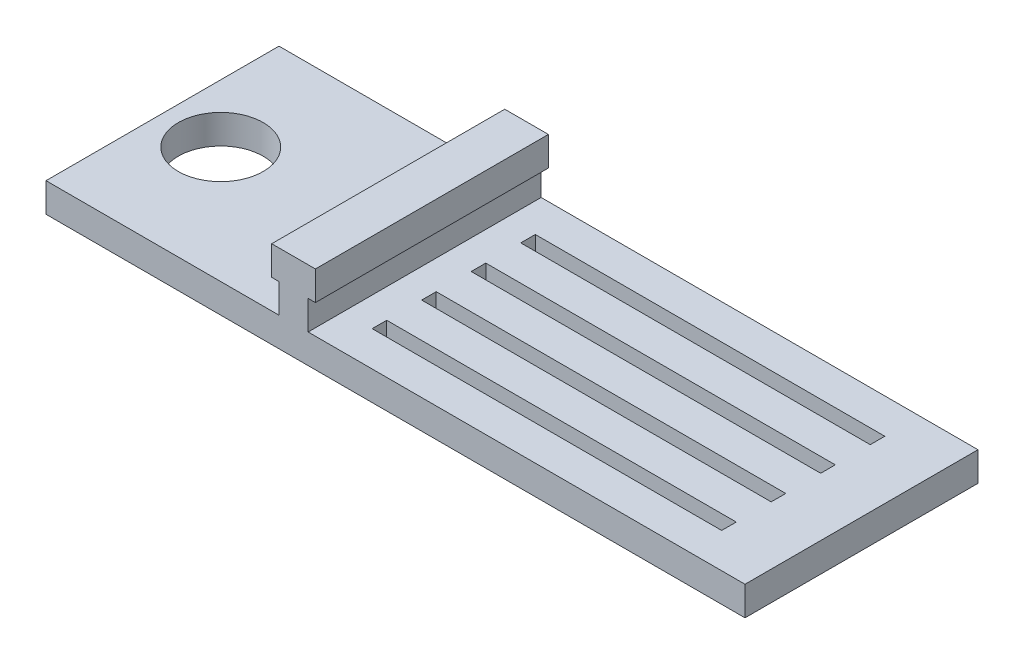
SolidWorks part; units mm, degrees
ref_plane "Front Plane" through (0, 0, 0) normal (0, 0, 1) x (1, 0, 0)
ref_plane "Top Plane" through (0, 0, 0) normal (0, 1, 0) x (1, 0, 0)
ref_plane "Right Plane" through (0, 0, 0) normal (1, 0, 0) x (0, 0, -1)
sketch "Sketch1" plane through (0, 0, 0) normal (0, 1, 0) x (1, 0, 0)
  line L1 (0, 0) -> (304.8, 0)
  line L2 (0, 0) -> (0, 101.6)
  line L3 (0, 101.6) -> (304.8, 101.6)
  line L4 (304.8, 0) -> (304.8, 101.6)
  dimension "D1" = 304.8
  dimension "4" = 101.6
extrude "Boss-Extrude1" add sketch "Sketch1" along normal blind 12.7
sketch "Sketch2" plane through (0, 12.7, 0) normal (0, 1, 0) x (1, 0, 0)
  line L1 (127, 21.5701) -> (279.4, 21.5701)
  line L2 (127, 21.5701) -> (127, 15.2201)
  line L3 (127, 15.2201) -> (279.4, 15.2201)
  line L4 (279.4, 21.5701) -> (279.4, 15.2201)
  line L5 (304.8, 0) -> (304.8, 101.6) construction
  line L6 (304.8, 101.6) -> (0, 101.6) construction
  line L7 (127, 36.8101) -> (279.4, 36.8101)
  line L8 (127, 36.8101) -> (127, 43.1601)
  line L9 (127, 43.1601) -> (279.4, 43.1601)
  line L10 (279.4, 36.8101) -> (279.4, 43.1601)
  line L11 (127, 58.4001) -> (279.4, 58.4001)
  line L12 (127, 58.4001) -> (127, 64.77)
  line L13 (127, 64.77) -> (279.4, 64.77)
  line L14 (279.4, 58.4001) -> (279.4, 64.77)
  line L15 (127, 80.01) -> (279.4, 80.01)
  line L16 (127, 80.01) -> (127, 86.36)
  line L17 (127, 86.36) -> (279.4, 86.36)
  line L18 (279.4, 80.01) -> (279.4, 86.36)
  point P6 (279.4, 18.3951)
  dimension "D1" = 6.35
  dimension "D2" = 15.24
  dimension "D3" = 25.4
  dimension "D4" = 152.4
  dimension "D5" = 6.35
  dimension "D6" = 6.3699
  dimension "D7" = 6.35
  dimension "D8" = 15.24
  dimension "D9" = 15.24
  dimension "D10" = 15.24
  dimension "D11" = 152.4
  dimension "D12" = 152.4
  dimension "D13" = 152.4
extrude "Cut-Extrude1" cut sketch "Sketch2" against normal through all
sketch "Sketch3" plane through (0, 12.7, 0) normal (0, 1, 0) x (1, 0, 0)
  line L0 (0, 101.6) -> (0, 0) construction
  line L1 (304.8, 101.6) -> (0, 101.6) construction
  circle A0 centre (25.4, 50.8) radius 18.5
  dimension "D1" = 25.4
  dimension "D2" = 50.8
extrude "Cut-Extrude2" cut sketch "Sketch3" against normal through all
sketch "Sketch6" plane through (0, 0, 0) normal (0, 0, 1) x (1, 0, 0)
  line L0 (101.6, 12.7) -> (101.6, 25.4)
  line L1 (101.6, 25.4) -> (98.425, 25.4)
  line L2 (98.425, 25.4) -> (98.425, 38.1)
  line L3 (98.425, 38.1) -> (117.475, 38.1)
  line L4 (117.475, 38.1) -> (117.475, 25.4)
  line L5 (117.475, 25.4) -> (114.3, 25.4)
  line L6 (114.3, 25.4) -> (114.3, 12.7)
  line L8 (114.3, 12.7) -> (101.6, 12.7)
  line L10 (0, 12.7) -> (0, 0) construction
  dimension "D1" = 12.7
  dimension "D2" = 101.6
  dimension "D4" = 12.7
  dimension "D5" = 12.7
  dimension "D6" = 12.7
extrude "Boss-Extrude2" add sketch "Sketch6" against normal blind 101.6
